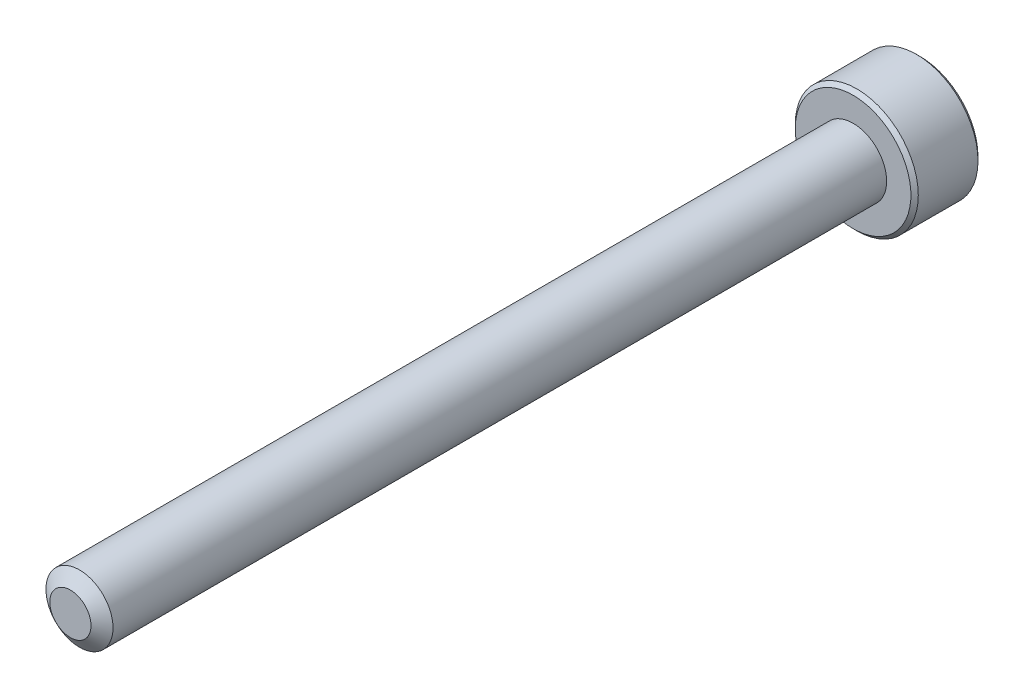
SolidWorks part; units mm, degrees
material "Alloy Steel"
ref_plane "Front Plane" through (0, 0, 0) normal (0, 0, 1) x (1, 0, 0)
ref_plane "Top Plane" through (0, 0, 0) normal (0, 1, 0) x (1, 0, 0)
ref_plane "Right Plane" through (0, 0, 0) normal (1, 0, 0) x (0, 0, -1)
sketch "Sketch1" plane through (0, 0, 0) normal (0, 0, 1) x (1, 0, 0)
  circle A0 centre (0, 0) radius 1.5
  dimension "OD" = 3
extrude "Extrude1" add sketch "Sketch1" against normal blind 35
sketch "Sketch2" plane through (0, 0, 0) normal (0, 0, 1) x (1, 0, 0)
  circle A0 centre (0, 0) radius 1.5 construction
  circle A1 centre (0, 0) radius 1.5
curve "Helix/Spiral1" [suppressed] pitch 0.5 height 35.5 turns 71 parameters "pitch"=0.5
sketch "Sketch3" plane through (0, 0, 0) normal (1, 0, 0) x (0, 0, -1)
  line L0 (-0.4375, 1.5) -> (-0.25, 1.1752)
  line L1 (-0.25, 1.1752) -> (-0.1875, 1.1752)
  line L2 (-0.1875, 1.1752) -> (0, 1.5)
  line L3 (-0.4375, 1.5) -> (0, 1.5)
  line L4 (-0.2187, 1.5) -> (-0.2187, 1.1752) construction
  line L5 (-0.3437, 1.3376) -> (-0.0937, 1.3376) construction
  line L6 (0, 1.5) -> (0, -1.5) construction
  line L7 (0, -1.5) -> (35, -1.5) construction
  point P11 (2.25, -1.5)
  dimension "D1" = 0.0625
  dimension "D2" = 0.25
  dimension "D3" = 60
  dimension "D4" = 2.25
sweep "Cut-Sweep1" [suppressed] cut profiles "Sketch3" path "Helix/Spiral1"
sketch "Sketch4" plane through (0, 0, 0) normal (1, 0, 0) x (0, 0, -1)
  line L0 (0.4053, 1.5) -> (0, 0.9212)
  line L1 (0, 0.9212) -> (0, 1.5)
  line L2 (0.4053, 1.5) -> (0, 1.5)
  line L3 (-0.4375, 1.5) -> (0, 1.5) construction
  line L4 (0, 0) -> (7.0209, 0) construction
  dimension "D1" = 55
  dimension "D2" = 0.254
revolve "Cut-Revolve1" cut sketch "Sketch4" angle 360 about L4
sketch "Sketch5" [suppressed] plane through (0, 0, 0) normal (1, 0, 0) x (0, 0, -1)
  line L0 (35, -1.1822) -> (35, 1.0703) construction
  line L1 (35, 1.5) -> (18.1202, 1.5)
  line L2 (35, 1.5) -> (35, 0)
  line L3 (35, 0) -> (18, 0)
  line L4 (18, 1.1698) -> (18, 0)
  line L5 (18.1202, 1.5) -> (18, 1.1698)
  line L6 (0, 0) -> (9.9695, 0) construction
  point P3 (18, 1.5)
  point P10 (18, 1.5)
  dimension "D1" = 0.3302
  dimension "Thread min" = 18
  dimension "D3" = 20
revolve "partially thread" [suppressed] add sketch "Sketch5" angle 360 about L6
sketch "Sketch6" plane through (0, 0, -35) normal (0, 0, -1) x (-1, 0, 0)
  circle A0 centre (0, 0) radius 2.75
  dimension "head dia" = 5.5
extrude "Extrude2" add sketch "Sketch6" along normal blind 3
sketch "Sketch7" plane through (0, 0, -38) normal (0, 0, -1) x (-1, 0, 0)
  line L1 (0, 1.4434) -> (-1.25, 0.7217)
  line L2 (-1.25, 0.7217) -> (-1.25, -0.7217)
  line L3 (-1.25, -0.7217) -> (0, -1.4434)
  line L4 (0, -1.4434) -> (1.25, -0.7217)
  line L5 (1.25, -0.7217) -> (1.25, 0.7217)
  line L6 (1.25, 0.7217) -> (0, 1.4434)
  circle A0 centre (0, 0) radius 1.25 construction
  dimension "hex dia" = 2.5
extrude "Cut-Extrude1" cut sketch "Sketch7" against normal blind 1.875
sketch "Sketch8" plane through (0, 0, -38) normal (0, 0, -1) x (-1, 0, 0)
  circle A0 centre (0, 0) radius 1.4434
extrude "Cut-Extrude2" cut sketch "Sketch8" against normal through all draft 45
chamfer "Chamfer1" distance 0.165 angle 45 2 edges at (-2.75, 0, -38) (-2.75, 0, -35)
sketch "Sketch9" plane through (0, 0, 0) normal (1, 0, 0) x (0, 0, -1)
  line L0 (0, 1.5) -> (0, -1.5) construction
  line L1 (2.75, 1.5) -> (2.75, -1.5) construction
  dimension "D1" = 2.75
sketch "Sketch10" plane through (0, 0, 0) normal (1, 0, 0) x (0, 0, -1)
  line L0 (35, 1.5) -> (35, 0)
  line L1 (35, 1.5) -> (34.875, 1.5)
  line L2 (34.875, 1.5) -> (34.2537, 0)
  line L3 (35, 0) -> (34.2537, 0)
  line L4 (35, 2.585) -> (35, -2.585) construction
  dimension "D1" = 22.5
  dimension "D2" = 0.125
revolve "Revolve1" [suppressed] add sketch "Sketch10" angle 360 about L3
equation "\"D3@Helix/Spiral1\" = \"screw length@Extrude1\"+\"pitch@Helix/Spiral1\""
equation "\"D1@Sketch3\" = \"pitch@Helix/Spiral1\"*.125"
equation "\"D2@Sketch3\" = \"pitch@Helix/Spiral1\"*.5"
equation "\"D1@Cut-Extrude1\" = \"hex dia@Sketch7\"*.75"
equation "\"D1@Chamfer1\" = \"head dia@Sketch6\"*.03"
equation "\"D1@Sketch9\" = \"pitch@Helix/Spiral1\"*5.5"
equation "\"D2@Sketch10\" = \"pitch@Helix/Spiral1\"*.25"
equation "\"D4@Sketch3\" = \"pitch@Helix/Spiral1\"*4.50"
